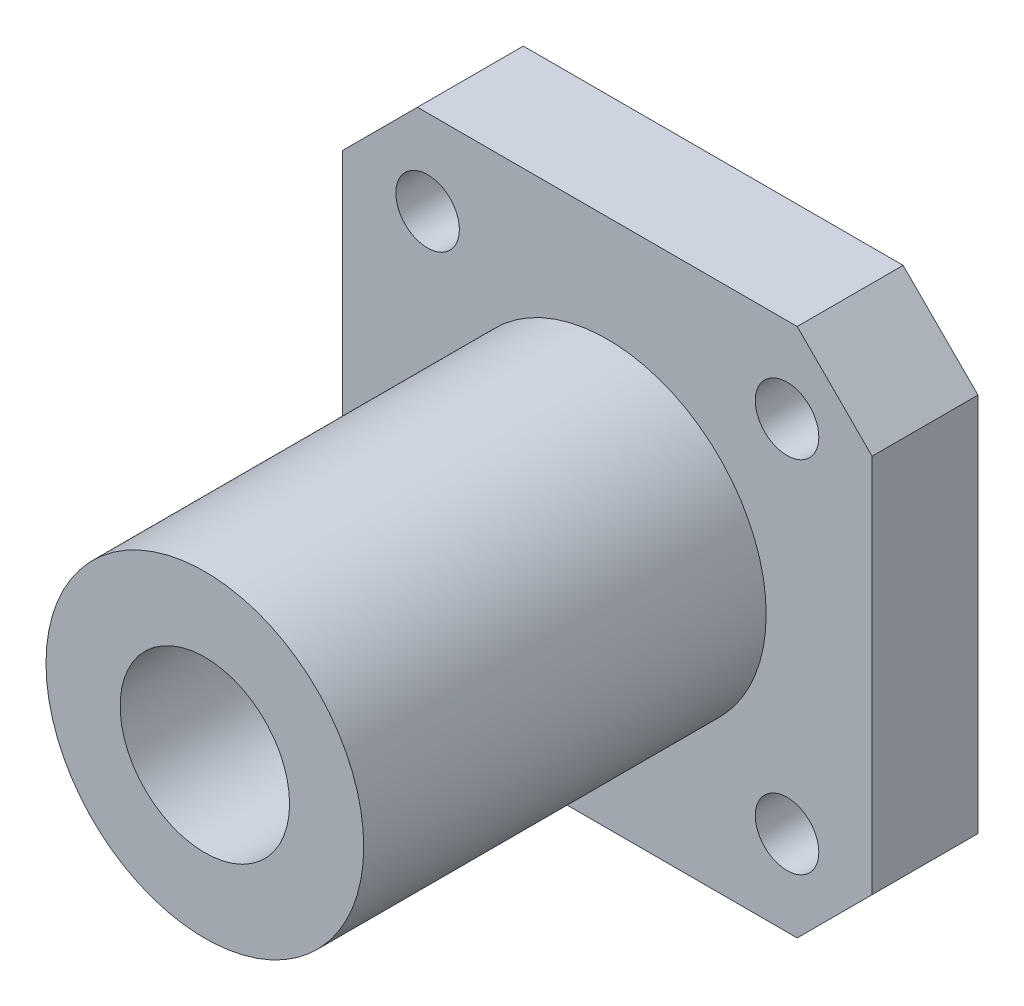
SolidWorks part; units mm, degrees
ref_plane "Front Plane" through (0, 0, 0) normal (0, 0, 1) x (1, 0, 0)
ref_plane "Top Plane" through (0, 0, 0) normal (0, 1, 0) x (1, 0, 0)
ref_plane "Right Plane" through (0, 0, 0) normal (1, 0, 0) x (0, 0, -1)
sketch "Sketch2" plane through (0, 0, 0) normal (0, 0, 1) x (1, 0, 0)
  line L0 (-12.5, 12.5) -> (12.5, -12.5) construction
  line L1 (-8.9645, 12.5) -> (8.9645, 12.5)
  line L2 (-12.5, 8.9645) -> (-12.5, -8.9645)
  line L3 (-8.9645, -12.5) -> (8.9645, -12.5)
  line L4 (12.5, 8.9645) -> (12.5, -8.9645)
  line L5 (-12.5, 8.9645) -> (-8.9645, 12.5)
  line L6 (-12.5, 12.5) -> (-12.5, 8.9645) construction
  line L7 (-12.5, 12.5) -> (-8.9645, 12.5) construction
  line L8 (8.9645, -12.5) -> (12.5, -8.9645)
  line L9 (8.9645, -12.5) -> (12.5, -12.5) construction
  line L10 (12.5, -8.9645) -> (12.5, -12.5) construction
  line L11 (-12.5, -8.9645) -> (-8.9645, -12.5)
  line L12 (8.9645, 12.5) -> (12.5, 8.9645)
  line L13 (8.9645, 12.5) -> (12.5, 12.5) construction
  line L14 (12.5, 12.5) -> (12.5, 8.9645) construction
  line L15 (-12.5, -8.9645) -> (-12.5, -12.5) construction
  line L16 (-12.5, -12.5) -> (-8.9645, -12.5) construction
  line L17 (-8.4853, 8.4853) -> (8.4853, -8.4853) construction
  line L18 (-8.4853, -8.4853) -> (8.4853, 8.4853) construction
  circle A0 centre (-8.4853, 8.4853) radius 1.5
  circle A1 centre (8.4853, -8.4853) radius 1.5
  circle A2 centre (8.4853, 8.4853) radius 1.5
  circle A3 centre (-8.4853, -8.4853) radius 1.5
  circle A4 centre (0, 0) radius 4
  dimension "D5" = 3
  dimension "D7" = 8
  dimension "D1" = 25
  dimension "D2" = 25
  dimension "D3" = 5
  dimension "D4" = 24
  dimension "D6" = 24
extrude "Boss-Extrude1" add sketch "Sketch2" along normal blind 5
sketch "Sketch3" plane through (0, 0, 5) normal (0, 0, 1) x (1, 0, 0)
  circle A0 centre (0, 0) radius 7.5
  circle A1 centre (0, 0) radius 4
  dimension "D1" = 15
  dimension "D2" = 8
extrude "Boss-Extrude2" add sketch "Sketch3" along normal blind 19
ref_axis "Z" through (0, 0, -1.2) along (0, 0, 1)
